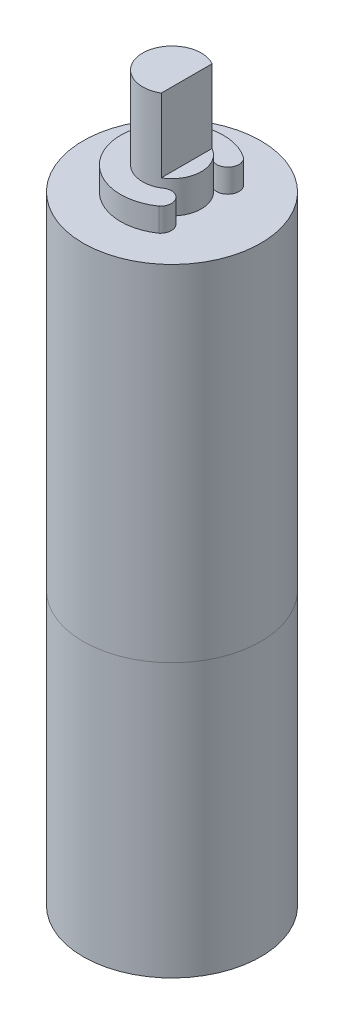
SolidWorks part; units mm, degrees
ref_plane "Front Plane" through (0, 0, 0) normal (0, 0, 1) x (1, 0, 0)
ref_plane "Top Plane" through (0, 0, 0) normal (0, 1, 0) x (1, 0, 0)
ref_plane "Right Plane" through (0, 0, 0) normal (1, 0, 0) x (0, 0, -1)
sketch "Sketch2" plane through (0, 0, 0) normal (1, 0, 0) x (0, 0, -1)
  line L0 (-3, 0) -> (3, 0) construction
  line L1 (0, 9.35) -> (0, -9.35) construction
  line L2 (116.8333, 245.5) -> (584.1667, 245.5) construction
  line L3 (-243.0708, 426.594) -> (-593.0708, 426.594) construction
  line L4 (-7.3679, 14.2754) -> (-7.3679, -9.35) construction
  point P2 (0, 0)
  point P6 (0, 0)
  dimension "D1" = 6
  dimension "D2" = 18.7
  dimension "D3" = 23.6254
sketch "Sketch3" plane through (0, 0, 0) normal (0, 1, 0) x (1, 0, 0)
  circle A0 centre (0, 0) radius 3.025
  dimension "D1" = 6.05
extrude "Boss-Extrude1" add sketch "Sketch3" along normal blind 9.3
sketch "Sketch4" plane through (0, 9.3, 0) normal (0, 1, 0) x (1, 0, 0)
  circle A0 centre (0, 0) radius 3.025
  dimension "D1" = 6.05
extrude "Boss-Extrude4" add sketch "Sketch4" along normal blind 11.75 separate body
sketch "Sketch5" plane through (0, 21.05, 0) normal (0, 1, 0) x (1, 0, 0)
  line L0 (-1, 0) -> (0.5, 0) construction
  line L1 (0.5, 0.866) -> (0.5, -0.866)
  line L2 (0.5, -0.866) -> (1.0001, -1.436) construction
  arc A0 (1.0001, 1.436) -> (1.0001, -1.436) centre (0, 0) ccw
  arc A1 (0.5, 0.866) -> (0.5903, -0.8072) centre (0, 0) ccw
  arc A2 (1.0001, -1.436) -> (0.5903, -0.8072) centre (0.7501, -1.151) ccw
  arc A3 (0.5, -0.866) -> (0.9098, -1.4949) centre (0.7501, -1.151) ccw construction
  arc A4 (0.9098, -1.4949) -> (1.0001, -1.436) centre (0.7501, -1.151) ccw construction
  arc A5 (0.5903, -0.8072) -> (0.5, -0.866) centre (0.7501, -1.151) ccw construction
  arc A6 (0.5903, -0.8072) -> (0.5903, 0.8072) centre (0, 0) ccw
  arc A7 (1.0001, 1.436) -> (0.5903, 0.8072) centre (0.7501, 1.151) cw
  arc A8 (1.0001, -1.436) -> (1.0001, 1.436) centre (0, 0) ccw construction
  arc A9 (0.5903, -0.8072) -> (0.5903, 0.8072) centre (0, 0) ccw construction
  arc A10 (0.5, 0.866) -> (-1, 0) centre (0, 0) ccw construction
  arc A11 (0.5903, 0.8072) -> (0.5, 0.866) centre (0, 0) ccw
  point P11 (0.5, 0)
  dimension "D1" = 3.5
  dimension "D2" = 2
  dimension "D3" = 1.5
extrude "Boss-Extrude5" add sketch "Sketch5" along normal blind 0.8 contours A11 A7 A0 A2 A1 region at (-1.0453, 21.05, 0)
extrude "Boss-Extrude6" add sketch "Sketch5<4>" along normal blind 3.6 contours L1 A1 region at (-0.1713, 21.05, 0)
sketch "Sketch5<4>" plane through (0, 21.05, 0) normal (0, 1, 0) x (1, 0, 0) same geometry as "Sketch5"
extrude "Boss-Extrude7" add sketch "Sketch5<5>" along normal blind 1.1 contours A6 A11 L1 A1 region at (0.705, 21.05, 0)
sketch "Sketch5<5>" plane through (0, 21.05, 0) normal (0, 1, 0) x (1, 0, 0) same geometry as "Sketch5"
